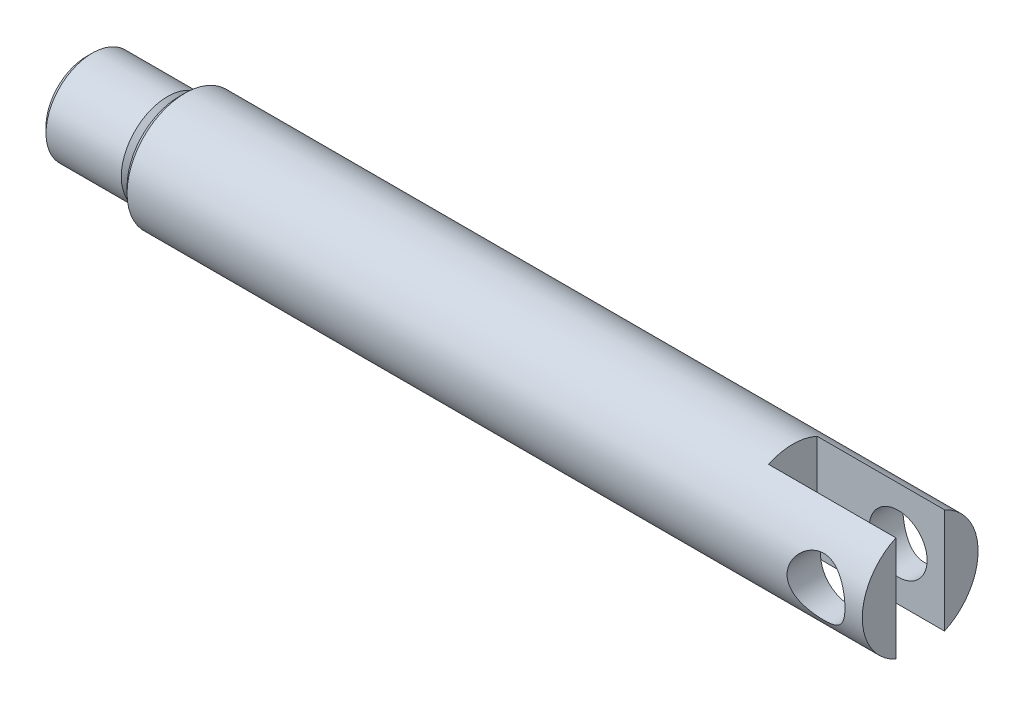
SolidWorks part; units mm, degrees
ref_plane "Front Plane" through (0, 0, 0) normal (0, 0, 1) x (1, 0, 0)
ref_plane "Top Plane" through (0, 0, 0) normal (0, 1, 0) x (1, 0, 0)
ref_plane "Right Plane" through (0, 0, 0) normal (1, 0, 0) x (0, 0, -1)
sketch "Sketch2" plane through (0, 0, 0) normal (0, 0, 1) x (1, 0, 0)
  line L0 (0, 0) -> (36, 0)
  line L1 (0, 0) -> (0, -2)
  line L2 (0, -2) -> (3.5, -2)
  line L3 (3.5, -2) -> (3.5, -1.75)
  line L4 (3.5, -1.75) -> (4, -1.75)
  line L5 (4, -1.75) -> (4, -2.5)
  line L6 (4, -2.5) -> (36, -2.5)
  line L7 (36, -2.5) -> (36, 0)
  dimension "D1" = 36
  dimension "D2" = 2
  dimension "D3" = 1.75
  dimension "D4" = 3.5
  dimension "D5" = 4
  dimension "D6" = 2.5
revolve "Revolve1" add sketch "Sketch2" angle 360 about L0
sketch "Sketch3" plane through (0, 0, 0) normal (0, 0, 1) x (1, 0, 0)
  line L1 (36, -2.5) -> (36, 2.5) construction
  circle A0 centre (34, 0) radius 1.25
  point P4 (0, 0)
  dimension "D1" = 2.5
  dimension "D2" = 2
extrude "Cut-Extrude1" cut sketch "Sketch3" against normal mid plane 10
sketch "Sketch4" plane through (36, 0, 0) normal (1, 0, 0) x (0, 0, -1)
  line L1 (-1.05, -2.9316) -> (1.05, -2.9316)
  line L2 (-1.05, -2.9316) -> (-1.05, 2.9316)
  line L3 (-1.05, 2.9316) -> (1.05, 2.9316)
  line L4 (1.05, -2.9316) -> (1.05, 2.9316)
  line L5 (-1.05, -2.9316) -> (1.05, 2.9316) construction
  line L6 (-1.05, 2.9316) -> (1.05, -2.9316) construction
  point P0 (0, 0)
  dimension "D1" = 2.1
extrude "Cut-Extrude2" cut sketch "Sketch4" against normal blind 5.5
chamfer "Chamfer1" distance 0.25 angle 45 3 edges at (0, 0, 2) (3.5, 0, 1.75) (4, 0, 2.5)
